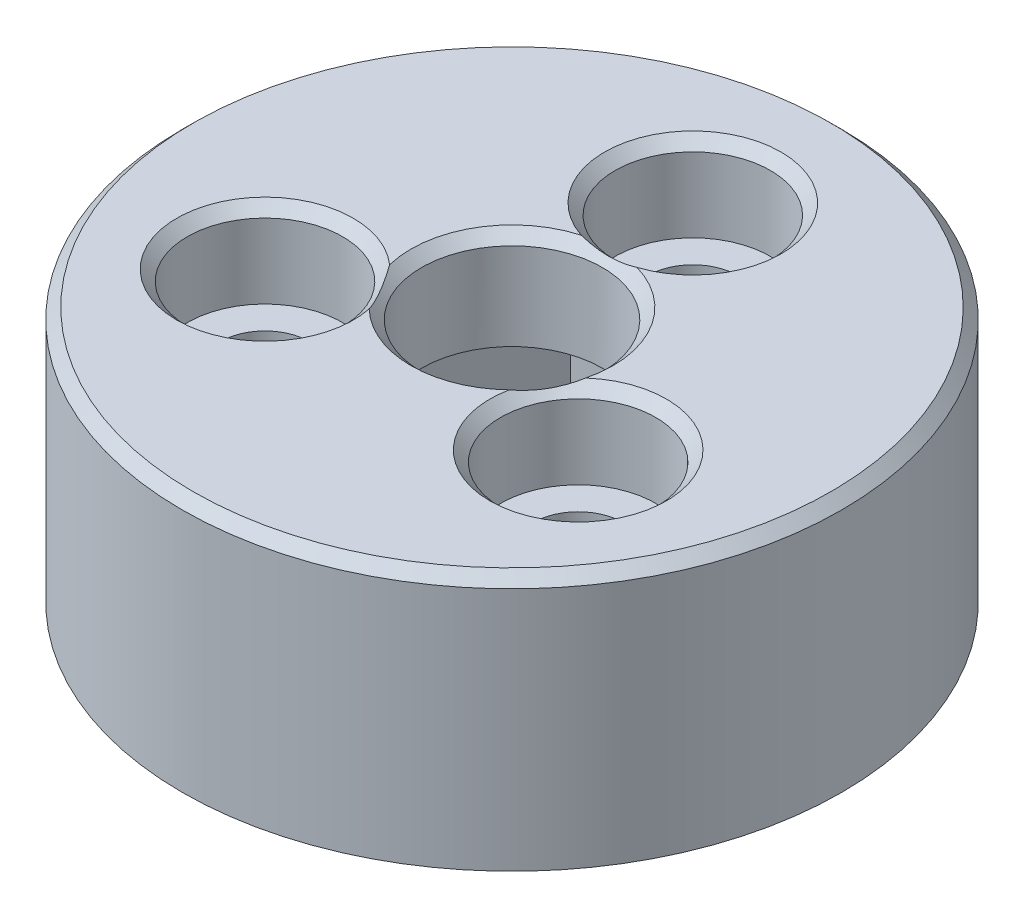
SolidWorks part; units mm, degrees
ref_plane "Front Plane" through (0, 0, 0) normal (0, 0, 1) x (1, 0, 0)
ref_plane "Top Plane" through (0, 0, 0) normal (0, 1, 0) x (1, 0, 0)
ref_plane "Right Plane" through (0, 0, 0) normal (1, 0, 0) x (0, 0, -1)
sketch "Sketch1" plane through (0, 0, 0) normal (0, 1, 0) x (1, 0, 0)
  circle A0 centre (0, 0) radius 15.5
  dimension "D1" = 31
extrude "Boss-Extrude1" add sketch "Sketch1" along normal blind 12
sketch "Sketch2" plane through (0, 12, 0) normal (0, 1, 0) x (1, 0, 0)
  circle A0 centre (0, 0) radius 8.5 construction
  circle A1 centre (0, 8.5) radius 2.1
  circle A2 centre (7.3612, -4.25) radius 2.1
  circle A3 centre (-7.3612, -4.25) radius 2.1
  point P12 (0, 0)
  dimension "D1" = 17
  dimension "D3" = 4.2
  dimension "D2" = 3
extrude "Cut-Extrude1" cut sketch "Sketch2" against normal through all
sketch "Sketch3" plane through (0, 12, 0) normal (0, 1, 0) x (1, 0, 0)
  circle A0 centre (0, 0) radius 4.25
  dimension "D1" = 8.5
extrude "Cut-Extrude2" cut sketch "Sketch3" against normal through all
sketch "Sketch4" plane through (0, 0, 0) normal (0, -1, 0) x (1, 0, 0)
  line L1 (3.7409, -6.4401) -> (7.4478, 0.0197)
  line L2 (7.4478, 0.0197) -> (3.7069, 6.4598)
  line L3 (3.7069, 6.4598) -> (-3.7409, 6.4401)
  line L4 (-3.7409, 6.4401) -> (-7.4478, -0.0197)
  line L5 (-7.4478, -0.0197) -> (-3.7069, -6.4598)
  line L6 (-3.7069, -6.4598) -> (3.7409, -6.4401)
  circle A0 centre (0, 0) radius 6.45 construction
  dimension "D1" = 12.9
extrude "Cut-Extrude3" cut sketch "Sketch4" against normal blind 7.4
sketch "Sketch5" plane through (0, 12, 0) normal (0, 1, 0) x (1, 0, 0)
  circle A0 centre (0, 8.5) radius 3.65
  circle A1 centre (7.3612, -4.25) radius 3.65
  circle A2 centre (-7.3612, -4.25) radius 3.65
  dimension "D1" = 7.3
extrude "Cut-Extrude4" cut sketch "Sketch5" against normal blind 4
chamfer "Chamfer1" distance 0.5 angle 45 5 edges at (0, 12, 15.5) (-7.3612, 12, 7.9) (7.3612, 12, 7.9) (0, 12, 4.25) (0, 12, -4.85)
fillet "Скругление1" radius 0.5 6 edges at (5.8175, 3.7, 2.8263) (5.3597, 3.7, 3.6143) (-5.3564, 3.7, 3.6249) (-5.81, 3.7, 2.8345) (0.4502, 3.7, -6.4488) (-0.4611, 3.7, -6.4512)
equation "\"D1@Cut-Extrude3\"=6.40мм+1"
